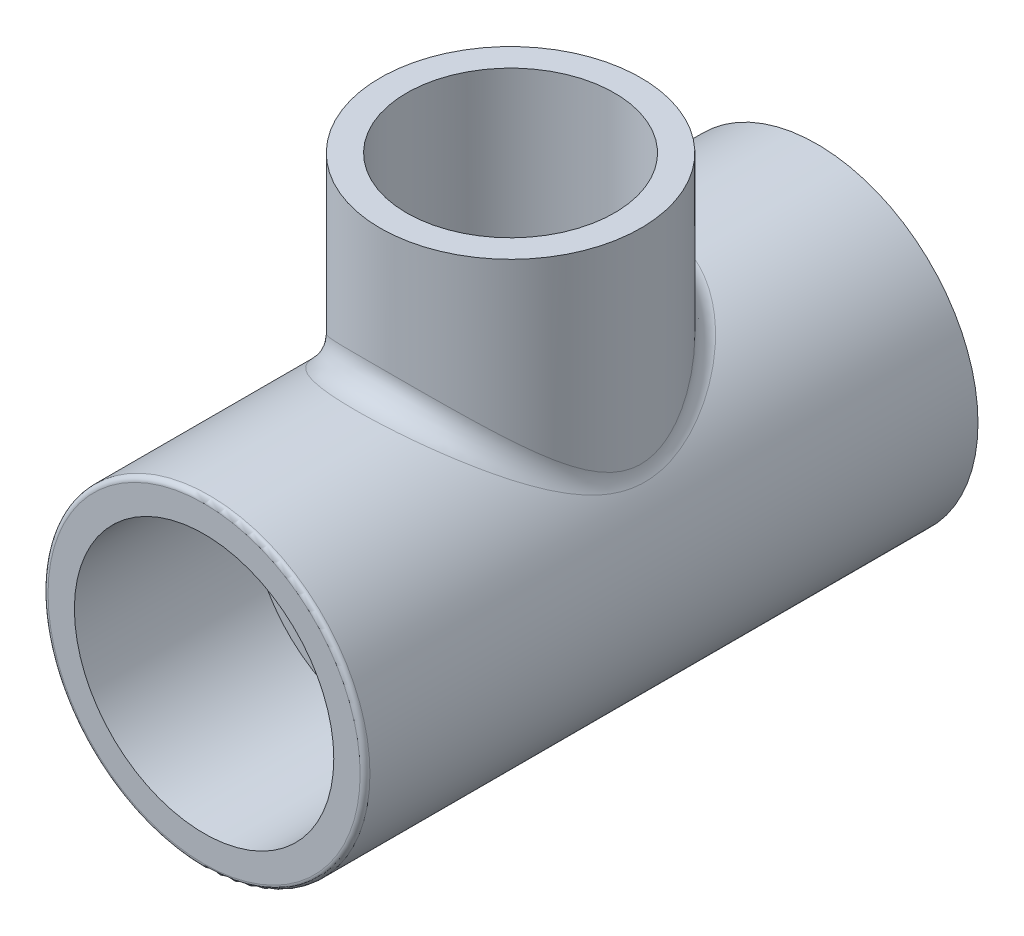
SolidWorks part; units mm, degrees
ref_plane "Front Plane" through (0, 0, 0) normal (0, 0, 1) x (1, 0, 0)
ref_plane "Top Plane" through (0, 0, 0) normal (0, 1, 0) x (1, 0, 0)
ref_plane "Right Plane" through (0, 0, 0) normal (1, 0, 0) x (0, 0, -1)
sketch "Sketch1" plane through (0, 0, 0) normal (0, 0, 1) x (1, 0, 0)
  circle A0 centre (0, 0) radius 656.5
  dimension "D1" = 1313
extrude "Boss-Extrude1" add sketch "Sketch1" along normal blind 1250 and the other way blind 1250
sketch "Sketch2" plane through (0, 0, 0) normal (0, 1, 0) x (1, 0, 0)
  circle A0 centre (0, 0) radius 531.5
  dimension "D1" = 1063
extrude "Boss-Extrude2" add sketch "Sketch2" along normal blind 1250
sketch "Sketch3" plane through (0, 1250, 0) normal (0, 1, 0) x (1, 0, 0)
  circle A0 centre (0, 0) radius 311
  dimension "D1" = 622
extrude "Cut-Extrude1" cut sketch "Sketch3" against normal through all
sketch "Sketch4" plane through (0, 1250, 0) normal (0, 1, 0) x (1, 0, 0)
  circle A0 centre (0, 0) radius 424
  dimension "D1" = 848
extrude "Cut-Extrude2" cut sketch "Sketch4" against normal through all
sketch "Sketch5" plane through (0, 0, 1250) normal (0, 0, 1) x (1, 0, 0)
  circle A0 centre (0, 0) radius 412
  dimension "D1" = 824
extrude "Cut-Extrude3" cut sketch "Sketch5" against normal through all
sketch "Sketch6" plane through (0, 0, 1250) normal (0, 0, 1) x (1, 0, 0)
  circle A0 centre (0, 0) radius 529
  dimension "D1" = 1058
extrude "Cut-Extrude4" cut sketch "Sketch6" against normal blind 720
fillet "Fillet1" radius 20 1 edges at (656.5, 0, 1250)
sketch "Sketch7" plane through (0, 0, -1250) normal (0, 0, -1) x (-1, 0, 0)
  circle A0 centre (0, 0) radius 529
  dimension "D1" = 1058
extrude "Cut-Extrude5" cut sketch "Sketch7" against normal blind 720
fillet "Fillet2" radius 100 1 edges at (-51.7907, 654.454, 528.9707)
